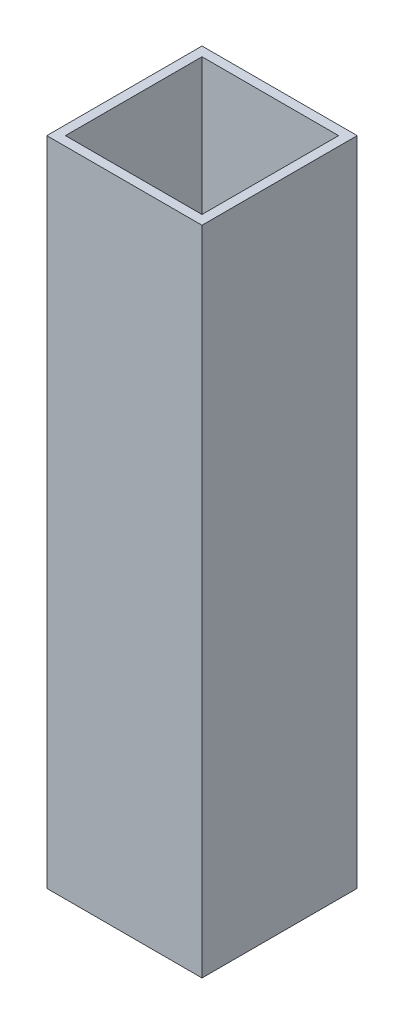
SolidWorks part; units mm, degrees
ref_plane "Front Plane" through (0, 0, 0) normal (0, 0, 1) x (1, 0, 0)
ref_plane "Top Plane" through (0, 0, 0) normal (0, 1, 0) x (1, 0, 0)
ref_plane "Right Plane" through (0, 0, 0) normal (1, 0, 0) x (0, 0, -1)
sketch "Sketch1" plane through (0, 0, 0) normal (0, 1, 0) x (1, 0, 0)
  line L0 (-26.6278, 1.8372) -> (-14.1278, -10.6628) construction
  line L1 (-26.6278, 1.8372) -> (-14.1278, 1.8372)
  line L2 (-26.6278, 1.8372) -> (-26.6278, -10.6628)
  line L3 (-26.6278, -10.6628) -> (-14.1278, -10.6628)
  line L4 (-14.1278, 1.8372) -> (-14.1278, -10.6628)
  line L5 (-26.6278, -10.6628) -> (-14.1278, 1.8372) construction
  line L7 (-25.8778, 1.0872) -> (-14.8778, 1.0872)
  line L8 (-25.8778, 1.0872) -> (-25.8778, -9.9128)
  line L9 (-25.8778, -9.9128) -> (-14.8778, -9.9128)
  line L10 (-14.8778, 1.0872) -> (-14.8778, -9.9128)
  line L11 (-25.8778, 1.0872) -> (-14.8778, -9.9128) construction
  line L12 (-25.8778, -9.9128) -> (-14.8778, 1.0872) construction
  point P4 (-20.3778, -4.4128)
extrude "Boss-Extrude3" add sketch "Sketch1" along normal blind 52.5
